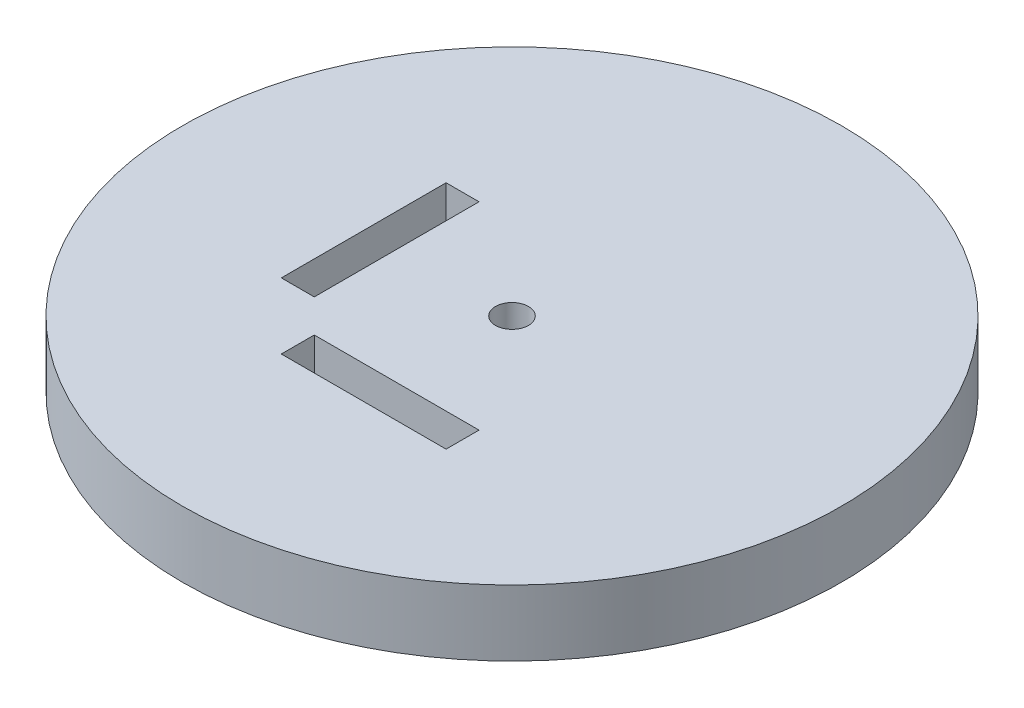
SolidWorks part; units mm, degrees
ref_plane "Front Plane" through (0, 0, 0) normal (0, 0, 1) x (1, 0, 0)
ref_plane "Top Plane" through (0, 0, 0) normal (0, 1, 0) x (1, 0, 0)
ref_plane "Right Plane" through (0, 0, 0) normal (1, 0, 0) x (0, 0, -1)
sketch "Sketch1" plane through (0, 0, 0) normal (0, 1, 0) x (1, 0, 0)
  circle A0 centre (0, 0) radius 50
  dimension "D1" = 100
extrude "Boss-Extrude1" add sketch "Sketch1" along normal blind 10
sketch "Sketch2" plane through (0, 10, 0) normal (0, 1, 0) x (1, 0, 0)
  line L0 (-17.5, -12.5) -> (-22.5, -12.5)
  line L1 (12.5, -17.5) -> (-12.5, -17.5)
  line L2 (12.5, -17.5) -> (12.5, -22.5)
  line L3 (12.5, -22.5) -> (-12.5, -22.5)
  line L4 (-12.5, -17.5) -> (-12.5, -22.5)
  line L5 (12.5, -17.5) -> (-12.5, -22.5) construction
  line L6 (12.5, -22.5) -> (-12.5, -17.5) construction
  line L7 (-17.5, -12.5) -> (-17.5, 12.5)
  line L8 (-17.5, 12.5) -> (-22.5, 12.5)
  line L9 (-22.5, -12.5) -> (-22.5, 12.5)
  circle A1 centre (0, 0) radius 2.5
  point P3 (0, -20)
  point P15 (0, 0)
  dimension "D1" = 25
  dimension "D2" = 20
  dimension "D3" = 5
  dimension "D4" = 2
extrude "Cut-Extrude1" cut sketch "Sketch2" against normal through all
ref_axis "Axis1" through (0, 0, 0) along (0, 1, 0)
